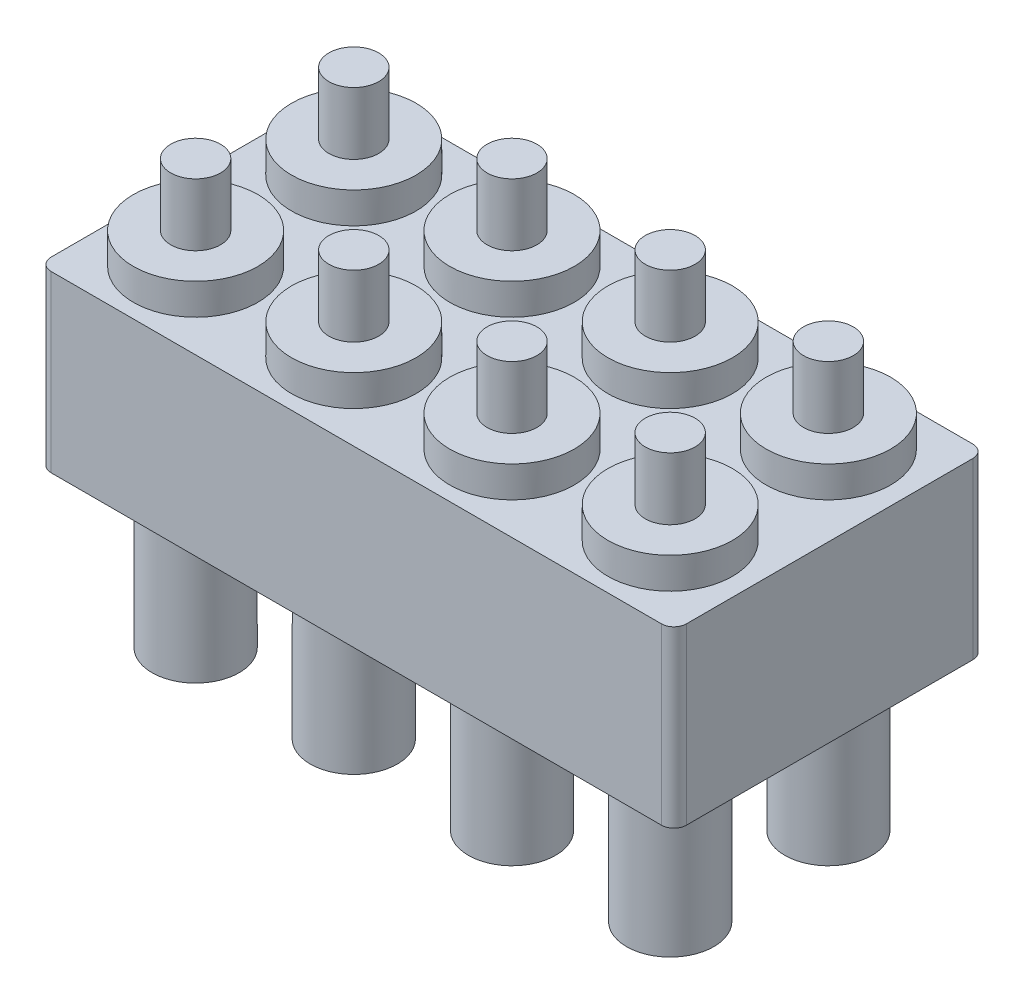
SolidWorks part; units mm, degrees
ref_plane "前视基准面" through (0, 0, 0) normal (0, 0, 1) x (1, 0, 0)
ref_plane "上视基准面" through (0, 0, 0) normal (0, 1, 0) x (1, 0, 0)
ref_plane "右视基准面" through (0, 0, 0) normal (1, 0, 0) x (0, 0, -1)
sketch "草图1" plane through (0, 0, 0) normal (0, 1, 0) x (1, 0, 0)
  line L1 (0, 0) -> (10.2, 0)
  line L2 (0, 0) -> (0, 5)
  line L3 (0, 5) -> (10.2, 5)
  line L4 (10.2, 0) -> (10.2, 5)
  dimension "D1" = 5
  dimension "D2" = 10.2
extrude "凸台-拉伸1" add sketch "草图1" along normal blind 2.8
sketch "草图2" plane through (0, 2.8, 0) normal (0, 1, 0) x (1, 0, 0)
  line L0 (-1.9071, 2.5) -> (11.9791, 2.5) construction
  line L1 (5.1, 7.0674) -> (5.1, -2.3874) construction
  circle A0 centre (1.29, 3.77) radius 1
  circle A1 centre (3.83, 3.77) radius 1
  circle A2 centre (6.37, 3.77) radius 1
  circle A3 centre (8.91, 3.77) radius 1
  circle A4 centre (3.83, 1.23) radius 1
  circle A5 centre (6.37, 1.23) radius 1
  circle A6 centre (8.91, 1.23) radius 1
  circle A7 centre (1.29, 1.23) radius 1
  dimension "D3" = 2
  dimension "D1" = 3.81
  dimension "D2" = 1.27
  dimension "D4" = 2
extrude "凸台-拉伸2" add sketch "草图2" along normal blind 0.5
sketch "草图3" plane through (0, 3.3, 0) normal (0, 1, 0) x (1, 0, 0)
  circle A0 centre (1.29, 1.23) radius 0.4
  circle A1 centre (3.83, 1.23) radius 0.4
  circle A2 centre (6.37, 1.23) radius 0.4
  circle A3 centre (8.91, 1.23) radius 0.4
  circle A4 centre (3.83, 3.77) radius 0.4
  circle A5 centre (6.37, 3.77) radius 0.4
  circle A6 centre (8.91, 3.77) radius 0.4
  circle A7 centre (1.29, 3.77) radius 0.4
  dimension "D1" = 0.8
  dimension "D2" = 2
extrude "凸台-拉伸3" add sketch "草图3" along normal blind 1
sketch "草图4" plane through (0, 3.3, 0) normal (0, 1, 0) x (1, 0, 0)
  circle A0 centre (1.29, 1.23) radius 0.7
  circle A1 centre (3.83, 1.23) radius 0.7
  circle A2 centre (6.37, 1.23) radius 0.7
  circle A3 centre (8.91, 1.23) radius 0.7
  circle A4 centre (3.83, 3.77) radius 0.7
  circle A5 centre (6.37, 3.77) radius 0.7
  circle A6 centre (8.91, 3.77) radius 0.7
  circle A7 centre (1.29, 3.77) radius 0.7
  dimension "D1" = 1.4
  dimension "D2" = 2
extrude "凸台-拉伸4" add sketch "草图4" against normal blind 5.8
sketch "草图5" plane through (0, -2.5, 0) normal (0, -1, 0) x (1, 0, 0)
  circle A0 centre (8.91, -1.23) radius 0.6
  circle A1 centre (6.37, -1.23) radius 0.6
  circle A2 centre (3.83, -1.23) radius 0.6
  circle A3 centre (1.29, -1.23) radius 0.6
  circle A4 centre (6.37, -3.77) radius 0.6
  circle A5 centre (3.83, -3.77) radius 0.6
  circle A6 centre (1.29, -3.77) radius 0.6
  circle A7 centre (8.91, -3.77) radius 0.6
  dimension "D1" = 1.2
  dimension "D2" = 2
extrude "切除-拉伸1" cut sketch "草图5" against normal blind 0.25
fillet "圆角1" radius 0.6 8 edges at (3.83, -2.25, -4.37) (6.37, -2.25, -4.37) (8.91, -2.25, -4.37) (8.91, -2.25, -1.83) (6.37, -2.25, -1.83) (3.83, -2.25, -1.83) (1.29, -2.25, -1.83) (1.29, -2.25, -4.37)
fillet "圆角2" radius 0.2 4 edges at (0, 1.4, 0) (10.2, 1.4, 0) (10.2, 1.4, -5) (0, 1.4, -5)
